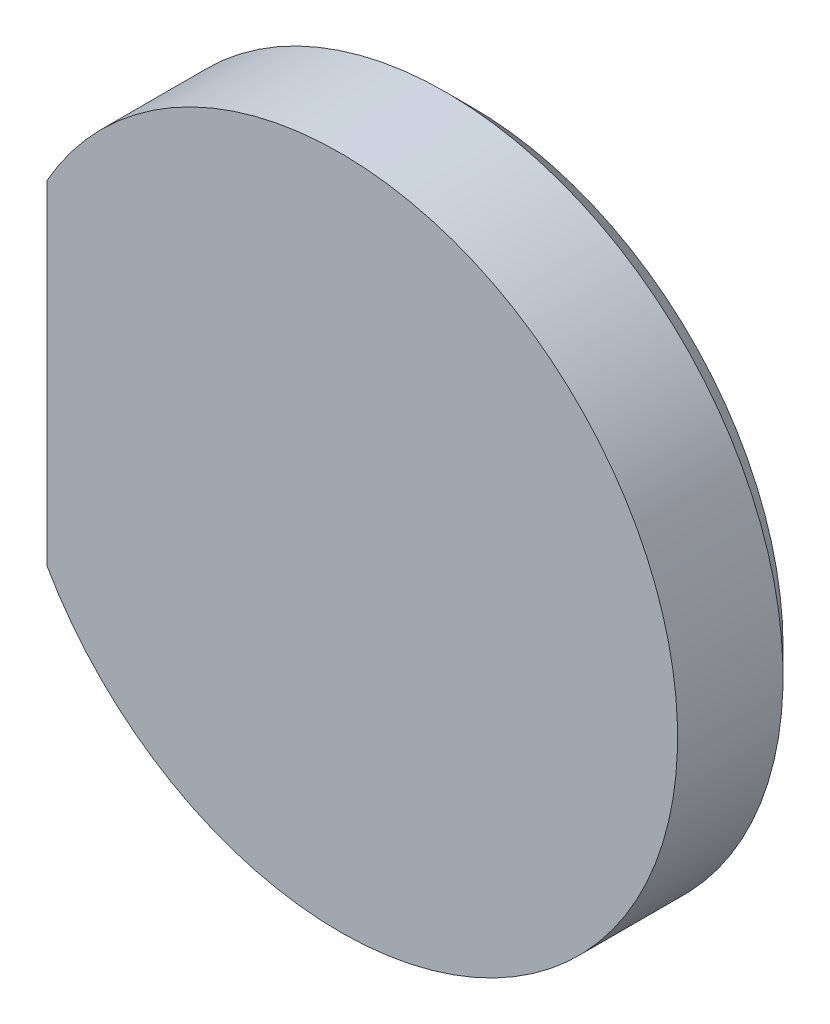
SolidWorks part; units mm, degrees
ref_plane "Спереди" through (0, 0, 0) normal (0, 0, 1) x (1, 0, 0)
ref_plane "Сверху" through (0, 0, 0) normal (0, 1, 0) x (1, 0, 0)
ref_plane "Справа" through (0, 0, 0) normal (1, 0, 0) x (0, 0, -1)
sketch "Эскиз1" plane through (0, 0, 0) normal (0, 0, 1) x (1, 0, 0)
  circle A0 centre (0, 0) radius 25.6
  dimension "D1" = 51.2
extrude "Бобышка-Вытянуть1" add sketch "Эскиз1" along normal blind 10
chamfer "Фаска1" distance 2 angle 45 1 edges at (25.6, 0, 0)
sketch "Эскиз2" plane through (0, 0, 10) normal (0, 0, 1) x (1, 0, 0)
  line L0 (-22.25, -12.6609) -> (-22.25, 12.6609)
  line L1 (-22.25, -12.5) -> (-22.25, -10) construction
  circle A0 centre (0, 0) radius 25.6 construction
  arc A1 (-22.25, 12.6609) -> (-22.25, -12.6609) centre (0, 0) ccw
  circle A2 centre (0, 0) radius 25.6 construction
extrude "Вырез-Вытянуть1" cut sketch "Эскиз2" against normal blind 2.5
sketch "Эскиз3" plane through (0, 0, 0) normal (0, 0, -1) x (-1, 0, 0)
  circle A0 centre (0, 0) radius 23.2
  dimension "D1" = 46.4
extrude "Вырез-Вытянуть2" cut sketch "Эскиз3" against normal offset from surface (7.5 mm away) 2.5 up to face at (1.675, 0, 10)
ref_plane "Плоскость1" through (0, -12.6609, 0) normal (0, 1, 0) x (1, 0, 0)
sketch "Эскиз5" plane through (0, 0, 0) normal (0, 0, -1) x (-1, 0, 0)
  line L0 (22.25, 6.571) -> (22.25, -6.571) construction
  line L1 (17.5672, 12.6609) -> (26.9328, 12.6609)
  line L2 (17.5672, 12.6609) -> (17.5672, -12.6609)
  line L3 (17.5672, -12.6609) -> (26.9328, -12.6609)
  line L4 (26.9328, 12.6609) -> (26.9328, -12.6609)
  line L5 (17.5672, 12.6609) -> (26.9328, -12.6609) construction
  line L6 (17.5672, -12.6609) -> (26.9328, 12.6609) construction
  line L7 (1.375, -12.6609) -> (-1.375, -12.6609) construction
  point P0 (22.25, 0)
extrude "Вырез-Вытянуть3" cut sketch "Эскиз5" against normal up to surface (7.5 mm away) up to face at (0.475, 0, 7.5)
fillet "Скругление2" radius 4 2 edges at (-19.4407, 12.6609, 3.75) (-19.4407, -12.6609, 3.75)
